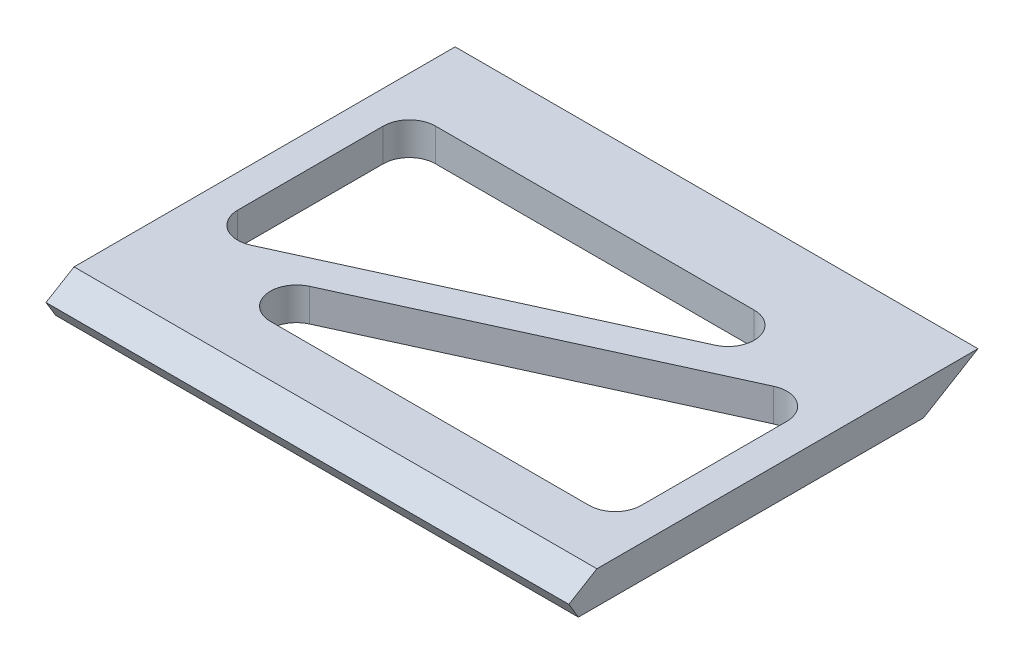
SolidWorks part; units mm, degrees
material "Balsa"
ref_plane "Front Plane" through (0, 0, 0) normal (0, 0, 1) x (1, 0, 0)
ref_plane "Top Plane" through (0, 0, 0) normal (0, 1, 0) x (1, 0, 0)
ref_plane "Right Plane" through (0, 0, 0) normal (1, 0, 0) x (0, 0, -1)
sketch "Sketch3" plane through (71.1933, 0, 0) normal (1, 0, 0) x (0, 0, -1)
  line L0 (56.968, 6.35) -> (46.3846, 0)
  line L1 (46.3846, 0) -> (-20.6804, 0)
  line L2 (-20.6804, 0) -> (-22.5302, 3.083)
  line L3 (-22.5302, 3.083) -> (-29.8236, 15.2385) construction
  line L5 (56.968, 6.35) -> (89.6384, 25.9523) construction
  line L6 (-22.5302, 3.083) -> (-17.0851, 6.35)
  line L7 (-17.0851, 6.35) -> (56.968, 6.35)
  point P11 (56.968, 6.35)
extrude "Boss-Extrude2" add sketch "Sketch3" against normal up to surface (101.6 mm away)
sketch "Sketch4" plane through (0, 6.35, 0) normal (0, 1, 0) x (1, 0, 0)
  line L0 (-30.4067, -17.0851) -> (-30.4067, 56.968) construction
  line L1 (-18.9767, 41.728) -> (42.949, 41.728)
  line L2 (-24.0567, 36.648) -> (-24.0567, 8.3732)
  line L3 (-2.1624, -7.1791) -> (59.7633, -7.1791)
  line L4 (64.8433, 26.1757) -> (64.8433, -2.0991)
  line L5 (-30.4067, 56.968) -> (71.1933, 56.968) construction
  line L6 (71.1933, 56.968) -> (71.1933, -17.0851) construction
  line L7 (-30.4067, -17.0851) -> (71.1933, -17.0851) construction
  line L8 (-16.8668, 3.7521) -> (45.0589, 32.0269)
  line L9 (-4.2724, 2.522) -> (57.6533, 30.7968)
  line L10 (-29.6117, -5.5575) -> (68.6464, 39.3064)
  arc A0 (-4.2724, 2.522) -> (-2.1624, -7.1791) centre (-2.1624, -2.0991) ccw
  arc A1 (59.7633, -7.1791) -> (64.8433, -2.0991) centre (59.7633, -2.0991) ccw
  arc A2 (57.6533, 30.7968) -> (64.8433, 26.1757) centre (59.7633, 26.1757) cw
  arc A3 (45.0589, 32.0269) -> (42.949, 41.728) centre (42.949, 36.648) ccw
  arc A4 (-18.9767, 41.728) -> (-24.0567, 36.648) centre (-18.9767, 36.648) ccw
  arc A5 (-16.8668, 3.7521) -> (-24.0567, 8.3732) centre (-18.9767, 8.3732) cw
  dimension "D7" = 5.08
  dimension "D1" = 6.35
  dimension "D2" = 15.24
  dimension "D3" = 6.35
  dimension "D4" = 9.906
  dimension "D5" = 3.175
  dimension "D6" = 3.175
extrude "Cut-Extrude1" cut sketch "Sketch4" against normal up to surface (6.35 mm away) contours A5 L8 A3 L1 A4 L2 | A2 L9 A0 L3 A1 L4 region at (4.1335, 6.35, -27.6167) region at (36.6531, 6.35, -6.9321) up to face at (20.3933, 0, -12.8521)
